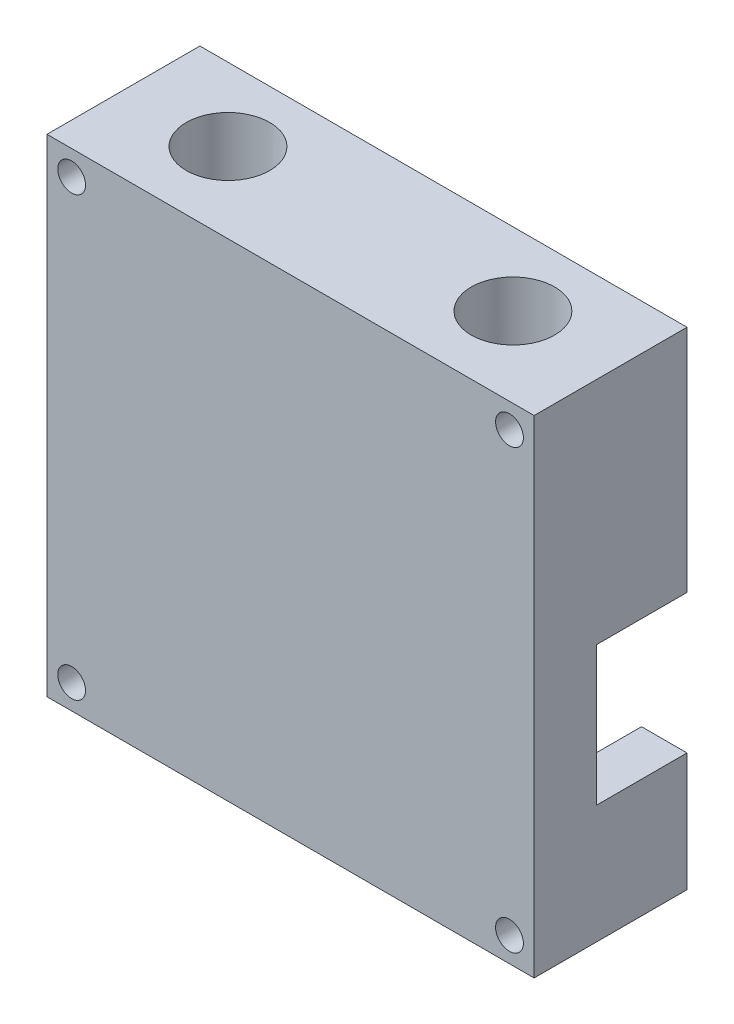
SolidWorks part; units mm, degrees
ref_plane "前视基准面" through (0, 0, 0) normal (0, 0, 1) x (1, 0, 0)
ref_plane "上视基准面" through (0, 0, 0) normal (0, 1, 0) x (1, 0, 0)
ref_plane "右视基准面" through (0, 0, 0) normal (1, 0, 0) x (0, 0, -1)
sketch "草图1" plane through (0, 0, 0) normal (0, 0, 1) x (1, 0, 0)
  line L1 (-35.0459, 35.0459) -> (35.0459, 35.0459)
  line L2 (-35.0459, 35.0459) -> (-35.0459, -35.0459)
  line L3 (-35.0459, -35.0459) -> (35.0459, -35.0459)
  line L4 (35.0459, 35.0459) -> (35.0459, -35.0459)
  line L5 (-35.0459, 35.0459) -> (35.0459, -35.0459) construction
  line L6 (-35.0459, -35.0459) -> (35.0459, 35.0459) construction
  circle A2 centre (-31.5, -31.5) radius 2
  circle A5 centre (-31.5, 31.5) radius 2
  circle A6 centre (31.5, 31.5) radius 2
  circle A7 centre (31.5, -31.5) radius 2
  point P1 (0, 0)
  point P17 (-0.5041, -0.5041)
  point P20 (0, 0)
  dimension "D1" = 4
extrude "凸台-拉伸1" add sketch "草图1" along normal blind 22
ref_plane "基准面4" through (0, 0, 0) normal (0, 0, 1) x (1, 0, 0)
sketch "草图2" plane through (0, 0, 0) normal (0, 0, 1) x (1, 0, 0)
  line L0 (-28.5, 25.5) -> (-13.5, 25.5)
  line L2 (28.5, 25.5) -> (28.5, -27.6)
  line L3 (28.5, -27.6) -> (-28.5, -27.6)
  line L4 (-28.5, 25.5) -> (-28.5, -27.6)
  line L5 (13.5, 29) -> (-13.5, 29)
  line L6 (13.5, 29) -> (13.5, 25.5)
  line L8 (-13.5, 29) -> (-13.5, 25.5)
  line L9 (13.5, 25.5) -> (28.5, 25.5)
extrude "切除-拉伸4" cut sketch "草图2" along normal blind 19
ref_plane "基准面5" through (0, 35.0459, 0) normal (0, 1, 0) x (1, 0, 0)
sketch "草图4" plane through (0, 35.0459, 0) normal (0, 1, 0) x (1, 0, 0)
  circle A0 centre (20.5, -10.5) radius 6
  circle A1 centre (-20.5, -10.5) radius 6
extrude "切除-拉伸5" cut sketch "草图4" against normal blind 15 contours A0
extrude "切除-拉伸6" cut sketch "草图4<3>" against normal blind 15
sketch "草图4<3>" plane through (0, 35.0459, 0) normal (0, 1, 0) x (1, 0, 0) same geometry as "草图4"
ref_plane "基准面6" through (35.0459, 0, 0) normal (1, 0, 0) x (0, 0, -1)
sketch "草图5" plane through (35.0459, 0, 0) normal (1, 0, 0) x (0, 0, -1)
  line L0 (0, -35.0459) -> (0, 35.0459) construction
  line L1 (0, 2) -> (-13, 2)
  line L2 (0, 2) -> (0, -18)
  line L3 (0, -18) -> (-13, -18)
  line L4 (-13, 2) -> (-13, -18)
extrude "切除-拉伸7" cut sketch "草图5" against normal blind 10
ref_plane "基准面7" through (0, -35.0459, 0) normal (0, -1, 0) x (-1, 0, 0)
sketch "草图6" plane through (0, -35.0459, 0) normal (0, -1, 0) x (-1, 0, 0)
  line L8 (35.0459, 0) -> (-35.0459, 0) construction
  line L9 (-28.5, 0) -> (28.5, 0)
  line L10 (-28.5, 0) -> (-28.5, -13)
  line L11 (-28.5, -13) -> (28.5, -13)
  line L12 (28.5, 0) -> (28.5, -13)
extrude "切除-拉伸8" cut sketch "草图6" against normal blind 16
